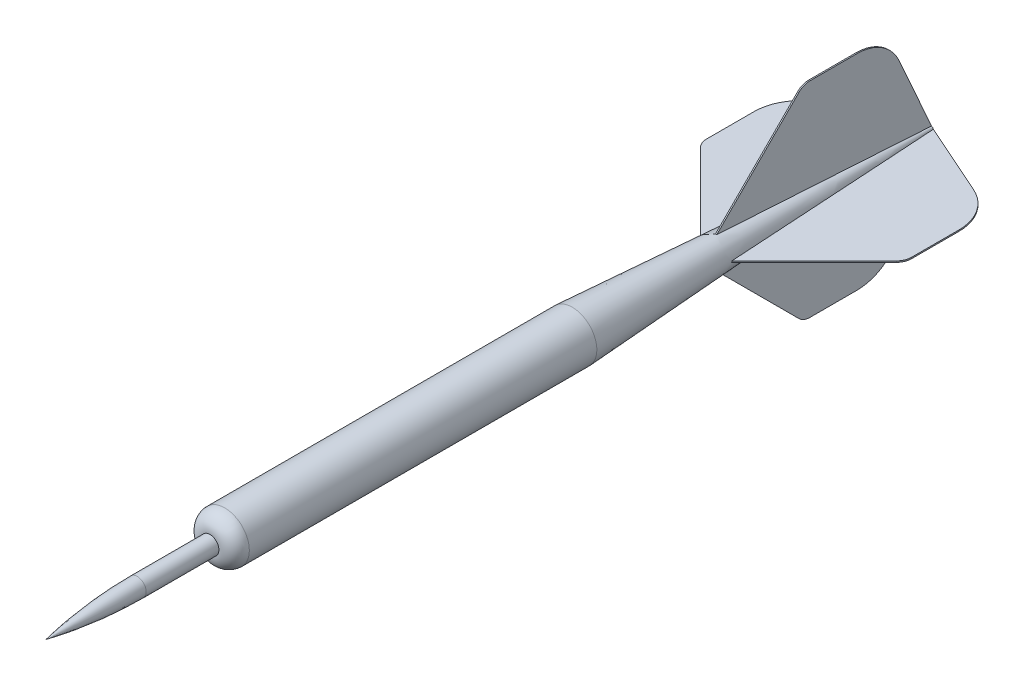
SolidWorks part; units mm, degrees
ref_plane "Front" through (0, 0, 0) normal (0, 0, 1) x (1, 0, 0)
ref_plane "Top" through (0, 0, 0) normal (0, 1, 0) x (1, 0, 0)
ref_plane "Right" through (0, 0, 0) normal (1, 0, 0) x (0, 0, -1)
sketch "Sketch1" plane through (0, 0, 0) normal (1, 0, 0) x (0, 0, -1)
  line L0 (0, 0) -> (-32, 0)
  line L2 (2.8878, 4.8) -> (70.72, 4.8)
  line L3 (70.72, 4.8) -> (140.72, 0.5)
  line L4 (140.72, 0.5) -> (140.72, 0)
  line L5 (140.72, 0) -> (0, 0)
  line L6 (-32, 0) -> (-39.4145, 0) construction
  line L7 (0, 1.75) -> (-14.1895, 1.75)
  arc A0 (0, 1.75) -> (2.8878, 4.8) centre (2.8878, 1.9079) cw
  arc A1 (-14.1895, 1.75) -> (-32, 0) centre (-14.1895, -89.7578) ccw
  point P12 (-14.1895, 1.75)
  dimension "D1" = 172.72
  dimension "D2" = 0.5
  dimension "D3" = 3.5
  dimension "D4" = 9.6
  dimension "D5" = 32
  dimension "D6" = 70
revolve "Dart" add sketch "Sketch1" angle 360 about L5
sketch "Sketch3" plane through (0, 0, 0) normal (1, 0, 0) x (0, 0, -1)
  line L0 (95.72, 0) -> (114.8413, 19.1213)
  line L1 (140.72, 0) -> (209.5416, 0) construction
  line L2 (116.9626, 20) -> (126.1934, 20)
  line L4 (140.72, 0) -> (95.72, 0)
  line L5 (134.4153, 14.6606) -> (140.72, 0.5)
  line L6 (140.72, 0.5) -> (140.72, 0)
  line L7 (140.72, -0.5) -> (140.72, 0.5) construction
  arc A0 (114.8413, 19.1213) -> (116.9626, 20) centre (116.9626, 17) cw
  arc A1 (126.1934, 20) -> (134.4153, 14.6606) centre (126.1934, 11) cw
  dimension "D3" = 3
  dimension "D6" = 9
  dimension "D1" = 40
  dimension "D2" = 45
  dimension "D4" = 45
  dimension "D5" = 66
extrude "Flight" add sketch "Sketch3" along normal mid plane 0.25
pattern_circular "Flights" count 4 over 360 about axis through (0, 0, -140.72) along (0, 0, -1) of "Flight"
sketch "Sketch4" plane through (0, 0, 0) normal (0, 0, 1) x (1, 0, 0)
  line L0 (15.5733, 0) -> (0, 0) construction
  line L1 (0, 0) -> (14.4278, 14.4278) construction
  point P3 (0, 0)
  point P5 (0, 0)
  dimension "D1" = 45
sketch "Sketch6" plane through (0, 0, 0) normal (1, 0, 0) x (0, 0, -1)
  line L0 (0, 0) -> (21.0498, 0) construction
ref_plane "45 Degreen Plane" through (0, 0, 0) normal (-0.7071, 0.7071, 0) x (0.7071, 0.7071, 0)
sketch "Flight Pocket Guide" plane through (0, 0, 0) normal (0, 0, 1) x (1, 0, 0)
  line L0 (0, 20) -> (0, 0) construction
  line L1 (0, 0) -> (20, 0) construction
  line L2 (-0.05, 20) -> (0.05, 20)
  line L3 (-0.75, 5.4772) -> (-0.75, 19.3)
  line L4 (0.75, 19.3) -> (0.75, 5.4772)
  line L5 (20, 0.05) -> (20, -0.05)
  line L6 (19.3, -0.75) -> (5.4772, -0.75)
  line L7 (19.3, 0.75) -> (5.4772, 0.75)
  line L8 (-5.4772, 0.75) -> (-19.3, 0.75)
  line L9 (-20, 0.05) -> (-20, -0.05)
  line L10 (-19.3, -0.75) -> (-5.4772, -0.75)
  line L11 (0.75, -5.4772) -> (0.75, -19.3)
  line L12 (0.05, -20) -> (-0.05, -20)
  line L13 (-0.75, -19.3) -> (-0.75, -5.4772)
  arc A0 (-4.5247, -1.4457) -> (-1.4457, -4.5247) centre (0, 0) ccw
  arc A1 (1.4457, -4.5247) -> (4.5247, -1.4457) centre (0, 0) ccw
  arc A2 (4.5247, 1.4457) -> (1.4457, 4.5247) centre (0, 0) ccw
  arc A3 (-1.4457, 4.5247) -> (-4.5247, 1.4457) centre (0, 0) ccw
  arc A4 (-0.05, 20) -> (-0.75, 19.3) centre (-0.05, 19.3) ccw
  arc A5 (0.05, 20) -> (0.75, 19.3) centre (0.05, 19.3) cw
  arc A6 (20, 0.05) -> (19.3, 0.75) centre (19.3, 0.05) ccw
  arc A7 (20, -0.05) -> (19.3, -0.75) centre (19.3, -0.05) cw
  arc A8 (0.75, -19.3) -> (0.05, -20) centre (0.05, -19.3) cw
  arc A9 (-0.05, -20) -> (-0.75, -19.3) centre (-0.05, -19.3) cw
  arc A10 (-20, -0.05) -> (-19.3, -0.75) centre (-19.3, -0.05) ccw
  arc A11 (-19.3, 0.75) -> (-20, 0.05) centre (-19.3, 0.05) ccw
  arc A12 (-0.75, 5.4772) -> (-1.4457, 4.5247) centre (-1.75, 5.4772) cw
  arc A13 (0.75, 5.4772) -> (1.4457, 4.5247) centre (1.75, 5.4772) ccw
  arc A14 (5.4772, 0.75) -> (4.5247, 1.4457) centre (5.4772, 1.75) cw
  arc A15 (5.4772, -0.75) -> (4.5247, -1.4457) centre (5.4772, -1.75) ccw
  arc A16 (0.75, -5.4772) -> (1.4457, -4.5247) centre (1.75, -5.4772) cw
  arc A17 (-0.75, -5.4772) -> (-1.4457, -4.5247) centre (-1.75, -5.4772) ccw
  arc A18 (-5.4772, -0.75) -> (-4.5247, -1.4457) centre (-5.4772, -1.75) cw
  arc A19 (-5.4772, 0.75) -> (-4.5247, 1.4457) centre (-5.4772, 1.75) ccw
  point P19 (0, 0)
  point P22 (0, 0)
  point P30 (20, 0.75)
  point P33 (20, -0.75)
  point P44 (-0.75, 4.6904)
  point P47 (0.75, 4.6904)
  point P50 (4.6904, 0.75)
  point P53 (4.6904, -0.75)
  point P56 (0.75, -4.6904)
  dimension "D1" = 9.5
  dimension "D4" = 0.7
  dimension "D5" = 1
  dimension "D2" = 40
  dimension "D3" = 1.5
sketch "Pin Pocket Guide" plane through (0, 0, 0) normal (0, 0, 1) x (1, 0, 0)
  circle A0 centre (0, 0) radius 2.5
  dimension "D1" = 5
sketch "Shaft Pocket Guide" plane through (0, 0, 0) normal (0, 0, 1) x (1, 0, 0)
  circle A0 centre (0, 0) radius 4.75
  point P4 (0, 0)
  point P5 (0, 0)
